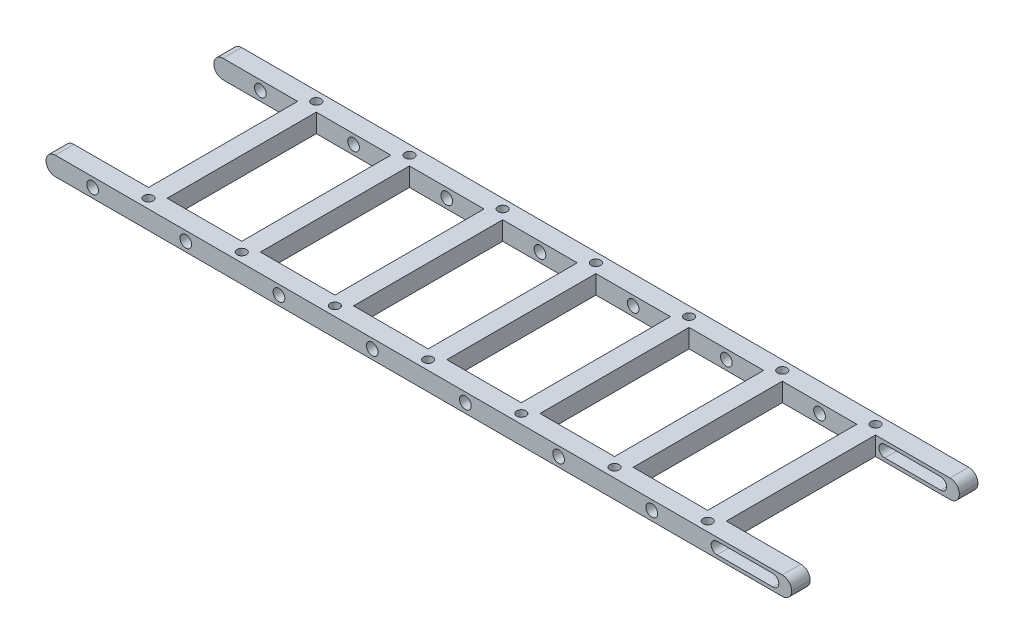
SolidWorks part; units mm, degrees
ref_plane "Front Plane" through (0, 0, 0) normal (0, 0, 1) x (1, 0, 0)
ref_plane "Top Plane" through (0, 0, 0) normal (0, 1, 0) x (1, 0, 0)
ref_plane "Right Plane" through (0, 0, 0) normal (1, 0, 0) x (0, 0, -1)
sketch "Sketch1" plane through (0, 0, 0) normal (0, 1, 0) x (1, 0, 0)
  line L0 (-127, 25.4) -> (-98.425, 25.4)
  line L1 (-127, 31.75) -> (127, 31.75)
  line L2 (-127, 31.75) -> (-127, 25.4)
  line L3 (-127, -31.75) -> (127, -31.75)
  line L4 (127, 31.75) -> (127, 25.4)
  line L5 (-127, 31.75) -> (127, -31.75) construction
  line L6 (-127, -31.75) -> (127, 31.75) construction
  line L8 (-127, -25.4) -> (-98.425, -25.4)
  line L10 (0, 31.75) -> (0, -31.75) construction
  line L11 (-3.175, 25.4) -> (-3.175, -25.4)
  line L12 (98.425, 25.4) -> (98.425, -25.4)
  line L14 (-3.175, 31.75) -> (-3.175, -31.75) construction
  line L15 (-28.575, 25.4) -> (-28.575, -25.4)
  line L16 (-34.925, 25.4) -> (-34.925, -25.4)
  line L17 (-60.325, 25.4) -> (-60.325, -25.4)
  line L18 (-66.675, 25.4) -> (-66.675, -25.4)
  line L19 (-92.075, 25.4) -> (-92.075, -25.4)
  line L22 (-98.425, 25.4) -> (-98.425, -25.4)
  line L23 (-127, -25.4) -> (-127, -31.75)
  line L24 (127, -25.4) -> (127, -31.75)
  line L26 (92.075, 25.4) -> (92.075, -25.4)
  line L27 (66.675, 25.4) -> (66.675, -25.4)
  line L28 (60.325, 25.4) -> (60.325, -25.4)
  line L29 (34.925, 25.4) -> (34.925, -25.4)
  line L30 (28.575, 25.4) -> (28.575, -25.4)
  line L31 (3.175, 25.4) -> (3.175, -25.4)
  line L34 (-92.075, 25.4) -> (-66.675, 25.4)
  line L35 (-92.075, -25.4) -> (-66.675, -25.4)
  line L36 (-28.575, -25.4) -> (-3.175, -25.4)
  line L37 (-60.325, 25.4) -> (-34.925, 25.4)
  line L38 (-28.575, 25.4) -> (-3.175, 25.4)
  line L39 (3.175, 25.4) -> (28.575, 25.4)
  line L40 (3.175, -25.4) -> (28.575, -25.4)
  line L41 (34.925, -25.4) -> (60.325, -25.4)
  line L42 (34.925, 25.4) -> (60.325, 25.4)
  line L43 (66.675, 25.4) -> (92.075, 25.4)
  line L44 (66.675, -25.4) -> (92.075, -25.4)
  line L47 (98.425, -25.4) -> (127, -25.4)
  line L48 (98.425, 25.4) -> (127, 25.4)
  line L49 (-60.325, -25.4) -> (-34.925, -25.4)
  point P0 (0, 0)
  dimension "D1" = 63.5
  dimension "D2" = 254
  dimension "D4" = 3.175
  dimension "D3" = 6.35
  dimension "D14" = 6.35
  dimension "D5" = 6.35
  dimension "D6" = 25.4
  dimension "D7" = 6.35
  dimension "D8" = 25.4
  dimension "D9" = 6.35
  dimension "D10" = 25.4
extrude "Boss-Extrude1" add sketch "Sketch1" against normal blind 6.35
sketch "Sketch2" plane through (0, 0, 31.75) normal (0, 0, 1) x (1, 0, 0)
  line L0 (-111.125, 0) -> (-111.125, -6.35) construction
  line L1 (0, 0) -> (0, -6.35) construction
  line L3 (-127, -6.35) -> (127, -6.35) construction
  line L15 (-66.675, 0) -> (-92.075, 0)
  line L16 (-92.075, 0) -> (-92.075, -6.35)
  line L17 (-92.075, -6.35) -> (-66.675, -6.35)
  line L18 (-66.675, -6.35) -> (-66.675, 0)
  line L19 (-66.675, 0) -> (-92.075, 0) construction
  line L20 (-92.075, 0) -> (-92.075, -6.35) construction
  line L21 (-92.075, -6.35) -> (-66.675, -6.35) construction
  line L22 (-66.675, -6.35) -> (-66.675, 0) construction
  circle A7 centre (-79.375, -3.175) radius 1.9939
  circle A8 centre (-47.625, -3.175) radius 1.9939
  circle A9 centre (-15.875, -3.175) radius 1.9939
  circle A15 centre (-111.125, -3.175) radius 1.9939
  circle A16 centre (15.875, -3.175) radius 1.9939
  circle A17 centre (47.625, -3.175) radius 1.9939
  circle A18 centre (79.375, -3.175) radius 1.9939
  circle A19 centre (111.125, -3.175) radius 1.9939
  point P3 (-79.375, 0)
  point P8 (-92.075, -3.175)
  dimension "D4" = 0
  dimension "D13" = 3.9878
  dimension "D14" = 3.9878
  dimension "D15" = 3.9878
  dimension "D2" = 3.9878
  dimension "D9" = 31.75
  dimension "D10" = 31.75
  dimension "D3" = 31.75
extrude "Cut-Extrude1" cut sketch "Sketch2" against normal up to surface (63.5 mm away) contours A15 | A7 | A8 | A17 | A9 | A16 | A19 | A18 region at (-79.375, -3.175, 31.75) region at (-47.625, -3.175, 31.75) region at (-111.125, -3.175, 31.75) region at (47.625, -3.175, 31.75) up to face at (0, -3.175, -31.75)
fillet "Fillet2" radius 3.175 8 edges at (-127, -6.35, 28.575) (-127, 0, 28.575) (-127, -6.35, -28.575) (-127, 0, -28.575) (127, -6.35, -28.575) (127, 0, -28.575) (127, -6.35, 28.575) (127, 0, 28.575)
sketch "Sketch3" plane through (0, 0, 31.75) normal (0, 0, 1) x (1, 0, 0)
  line L0 (101.6, -3.175) -> (120.65, -3.175) construction
  line L1 (101.6, -1.175) -> (120.65, -1.175)
  line L2 (101.6, -5.175) -> (120.65, -5.175)
  arc A0 (101.6, -1.175) -> (101.6, -5.175) centre (101.6, -3.175) ccw
  arc A1 (120.65, -5.175) -> (120.65, -1.175) centre (120.65, -3.175) ccw
  circle A2 centre (111.125, -3.175) radius 1.9939 construction
  circle A3 centre (111.125, -3.175) radius 1.9939 construction
  point P3 (111.125, -3.175)
  dimension "D2" = 2
  dimension "D1" = 19.05
extrude "Cut-Extrude2" cut sketch "Sketch3" against normal through all
sketch "Sketch4" plane through (0, 0, 0) normal (0, 1, 0) x (1, 0, 0)
  line L0 (-92.075, 0) -> (-98.425, 0) construction
  line L1 (-92.075, 25.4) -> (-92.075, -25.4) construction
  line L2 (-123.825, 28.575) -> (123.825, 28.575) construction
  line L3 (-123.825, -28.575) -> (123.825, -28.575) construction
  line L12 (-98.425, -25.4) -> (-123.825, -25.4)
  line L13 (-123.825, -25.4) -> (-123.825, -31.75)
  line L14 (-123.825, -31.75) -> (123.825, -31.75)
  line L15 (123.825, -31.75) -> (123.825, -25.4)
  line L16 (123.825, -25.4) -> (98.425, -25.4)
  line L17 (98.425, -25.4) -> (98.425, 25.4)
  line L18 (98.425, 25.4) -> (123.825, 25.4)
  line L19 (123.825, 25.4) -> (123.825, 31.75)
  line L20 (123.825, 31.75) -> (-123.825, 31.75)
  line L21 (-123.825, 31.75) -> (-123.825, 25.4)
  line L22 (-123.825, 25.4) -> (-98.425, 25.4)
  line L23 (-98.425, 25.4) -> (-98.425, -25.4)
  line L24 (-98.425, -25.4) -> (-123.825, -25.4) construction
  line L25 (-123.825, -25.4) -> (-123.825, -31.75) construction
  line L26 (-123.825, -31.75) -> (123.825, -31.75) construction
  line L27 (123.825, -31.75) -> (123.825, -25.4) construction
  line L28 (123.825, -25.4) -> (98.425, -25.4) construction
  line L29 (98.425, -25.4) -> (98.425, 25.4) construction
  line L30 (98.425, 25.4) -> (123.825, 25.4) construction
  line L31 (123.825, 25.4) -> (123.825, 31.75) construction
  line L32 (123.825, 31.75) -> (-123.825, 31.75) construction
  line L33 (-123.825, 31.75) -> (-123.825, 25.4) construction
  line L34 (-123.825, 25.4) -> (-98.425, 25.4) construction
  line L35 (-98.425, 25.4) -> (-98.425, -25.4) construction
  circle A0 centre (-95.25, 28.575) radius 1.5875
  circle A2 centre (-63.5, 28.575) radius 1.5875
  circle A3 centre (-31.75, 28.575) radius 1.5875
  circle A4 centre (0, 28.575) radius 1.5875
  circle A5 centre (31.75, 28.575) radius 1.5875
  circle A6 centre (63.5, 28.575) radius 1.5875
  circle A7 centre (95.25, 28.575) radius 1.5875
  circle A8 centre (95.25, -28.575) radius 1.5875
  circle A9 centre (63.5, -28.575) radius 1.5875
  circle A10 centre (31.75, -28.575) radius 1.5875
  circle A11 centre (0, -28.575) radius 1.5875
  circle A12 centre (-31.75, -28.575) radius 1.5875
  circle A13 centre (-63.5, -28.575) radius 1.5875
  circle A14 centre (-95.25, -28.575) radius 1.5875
  point P10 (-95.25, 28.575)
  point P14 (-95.25, 0)
  point P16 (-123.825, 28.575)
  point P26 (0, 0)
  point P52 (-95.25, -28.575)
  dimension "D2" = 3.175
  dimension "D5" = 31.75
  dimension "D1" = 0
  dimension "D4" = 7
extrude "Cut-Extrude3" cut sketch "Sketch4" against normal through all
